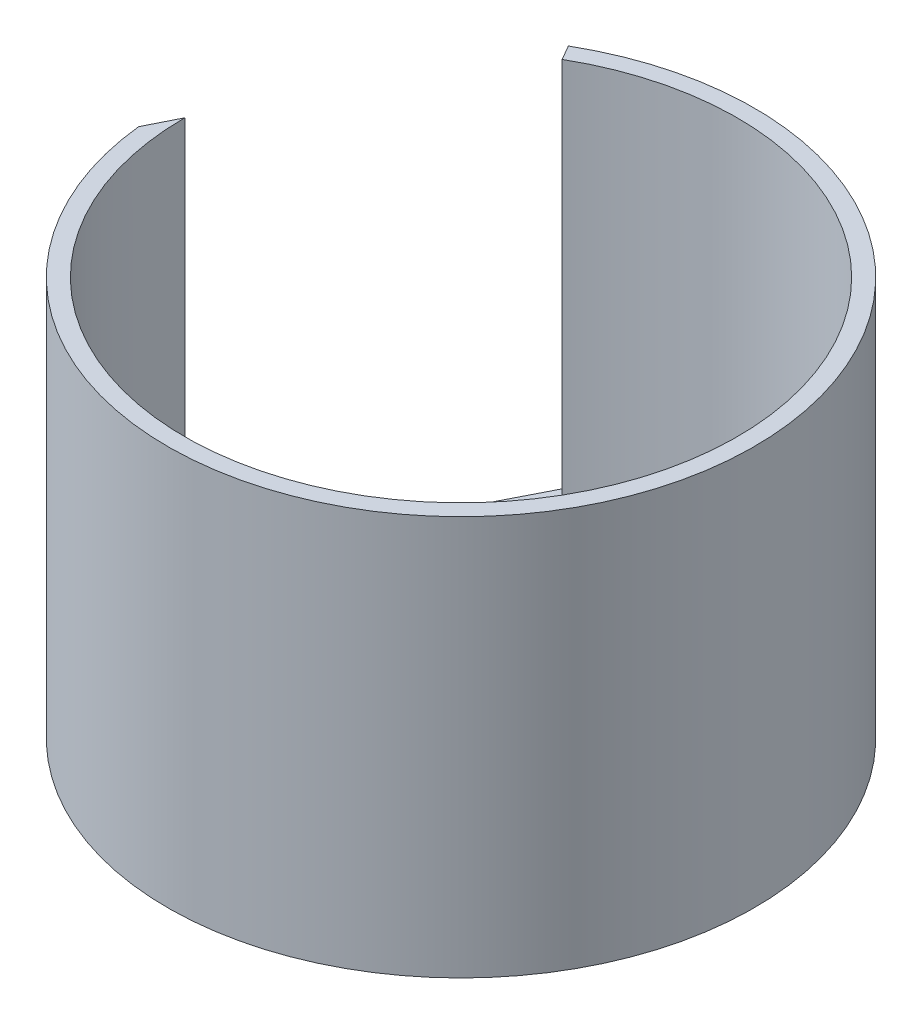
SolidWorks part; units mm, degrees
ref_plane "Front Plane" through (0, 0, 0) normal (0, 0, 1) x (1, 0, 0)
ref_plane "Top Plane" through (0, 0, 0) normal (0, 1, 0) x (1, 0, 0)
ref_plane "Right Plane" through (0, 0, 0) normal (1, 0, 0) x (0, 0, -1)
sketch "Sketch1" plane through (0, 0, 0) normal (0, 1, 0) x (1, 0, 0)
  circle A0 centre (0, 0) radius 41.275
  dimension "D1" = 82.55
extrude "Extrude-Thin1" add sketch "Sketch1" along normal blind 57.15 thin thin type one direction wall 2.54
sketch "Sketch4" plane through (0, 57.15, 0) normal (0, 1, 0) x (1, 0, 0)
  line L0 (-41.275, 0) -> (-43.815, 0)
  line L1 (-20.6375, 35.7452) -> (-21.9075, 37.9449)
  arc A0 (-21.9075, 37.9449) -> (-43.815, 0) centre (0, 0) ccw
  arc A1 (-20.6375, 35.7452) -> (-41.275, 0) centre (0, 0) ccw
  circle A2 centre (0, 0) radius 43.815 construction
  dimension "D1" = 2.54
  dimension "D2" = 60
extrude "Cut-Extrude12" cut sketch "Sketch4" against normal through all
chamfer "Chamfer1" distance 5.08 distance2 2.54 1 edges at (-43.815, 28.575, 0) first distance on face at (2.5418, 28.575, 1.4675)
sketch "Sketch5" plane through (0, 0, 0) normal (0, -1, 0) x (1, 0, 0)
  line L0 (-21.9075, -37.9449) -> (-43.5732, 4.5965)
  arc A0 (-21.9075, -37.9449) -> (-43.5732, 4.5965) centre (0, 0) ccw
  arc A1 (-21.9075, -37.9449) -> (-43.5732, 4.5965) centre (0, 0) ccw construction
extrude "Boss-Extrude1" add sketch "Sketch5" along normal blind 2.54
